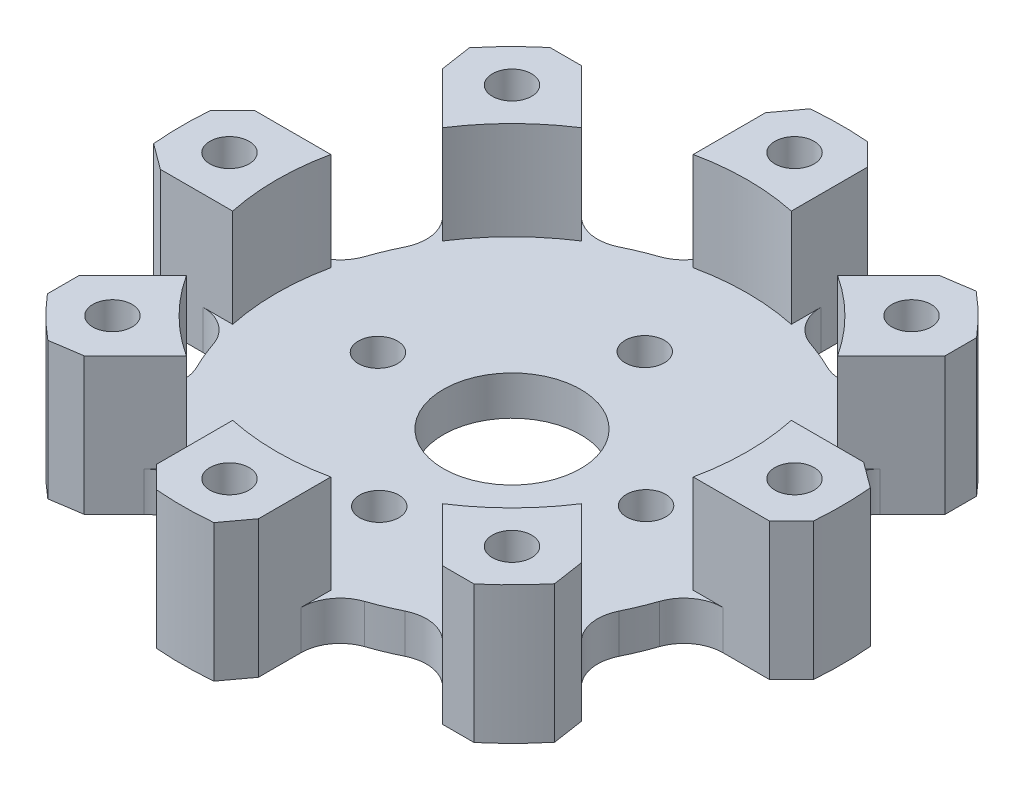
SolidWorks part; units mm, degrees
material "Nylon 101"
ref_plane "Front" through (0, 0, 0) normal (0, 0, 1) x (1, 0, 0)
ref_plane "Top" through (0, 0, 0) normal (0, 1, 0) x (1, 0, 0)
ref_plane "Right" through (0, 0, 0) normal (1, 0, 0) x (0, 0, -1)
sketch "Sketch1" plane through (0, 0, 0) normal (0, 1, 0) x (1, 0, 0)
  circle A0 centre (0, 0) radius 38.1
  dimension "D1" = 76.2
extrude "Base Extrude" add sketch "Sketch1" along normal blind 6.35
sketch "Sketch2" plane through (0, 0, 0) normal (0, 1, 0) x (1, 0, 0)
  line L0 (-7.9375, 37.264) -> (-7.9375, 52.7461)
  line L1 (7.9375, 37.264) -> (7.9375, 52.7461)
  circle A0 centre (0, 0) radius 45.72 construction
  circle A1 centre (0, 0) radius 38.1 construction
  arc A2 (7.9375, 37.264) -> (-7.9375, 37.264) centre (0, 0) ccw
  arc A4 (7.9375, 52.7461) -> (-7.9375, 52.7461) centre (0, 0) ccw
  circle A5 centre (0, 0) radius 53.34 construction
  point P5 (0, 38.1)
  dimension "D1" = 91.44
  dimension "D2" = 7.62
  dimension "D3" = 15.875
extrude "Column" add sketch "Sketch2" along normal blind 22.225
sketch "Sketch3" plane through (0, 0, 0) normal (0, 1, 0) x (1, 0, 0)
  circle A0 centre (0, 45.72) radius 3.175
  circle A1 centre (0, 0) radius 45.72 construction
  dimension "D1" = 91.44
  dimension "D2" = 6.35
extrude "Fastener Hole Cut 1" cut sketch "Sketch3" along normal through all
fillet "Relief Fillets" radius 6.35 2 edges at (-7.9375, 3.175, -37.264) (7.9375, 3.175, -37.264)
chamfer "Cosmetic Chamfer" distance 3.175 angle 45 2 edges at (7.9375, 11.1125, -52.7461) (-7.9375, 11.1125, -52.7461) first distance on face at (7.9375, 9.525, -44.0338) first distance on face at (0, 11.1125, -53.0431)
pattern_circular "Column and Hole Pattern" count 8 over 360 about axis through (0, 0, 0) along (0, 1, 0) of "Cosmetic Chamfer", "Column", "Fastener Hole Cut 1", "Relief Fillets"
sketch "Sketch4" plane through (0, 0, 0) normal (0, 1, 0) x (1, 0, 0)
  circle A0 centre (0, 0) radius 11.1125
  dimension "D1" = 22.225
extrude "Bearing Hole Cut" cut sketch "Sketch4" along normal through all
sketch "Sketch5" plane through (0, 0, 0) normal (0, 1, 0) x (1, 0, 0)
  line L0 (-0.0551, 11.1124) -> (-0.2645, 53.3393) construction
  line L1 (0, 0) -> (-0.0551, 11.1124) construction
  circle A0 centre (0, 0) radius 21.59 construction
  arc A1 (4.3459, 53.1627) -> (-4.8729, 53.117) centre (0, 0) ccw construction
  circle A2 centre (0, 0) radius 11.1125 construction
  circle A4 centre (-0.107, 21.5897) radius 3.175
  dimension "D1" = 6.35
  dimension "D2" = 43.18
extrude "Fastener Hole Cut 2" cut sketch "Sketch5" along normal through all
pattern_circular "Fastener Hole Cut 2 Pattern" count 4 over 360 about axis through (0, 22.225, 0) along (0, -1, 0) of "Fastener Hole Cut 2"
sketch "Sketch6" plane through (0, 0, 0) normal (0, 1, 0) x (1, 0, 0)
  line L1 (6.4158, 45.72) -> (3.2079, 51.2763)
  line L2 (3.2079, 51.2763) -> (-3.2079, 51.2763)
  line L3 (-3.2079, 51.2763) -> (-6.4158, 45.72)
  line L4 (-6.4158, 45.72) -> (-3.2079, 40.1638)
  line L5 (-3.2079, 40.1638) -> (3.2079, 40.1638)
  line L6 (3.2079, 40.1638) -> (6.4158, 45.72)
  circle A0 centre (0, 45.72) radius 5.5562 construction
  dimension "D1" = 11.1125
extrude "Hexagonal Counterbore" cut sketch "Sketch6" along normal blind 10.668
pattern_circular "Hexagonal Counterbore Pattern" count 8 over 360 about axis through (0, 6.35, 0) along (0, -1, 0) of "Hexagonal Counterbore"
